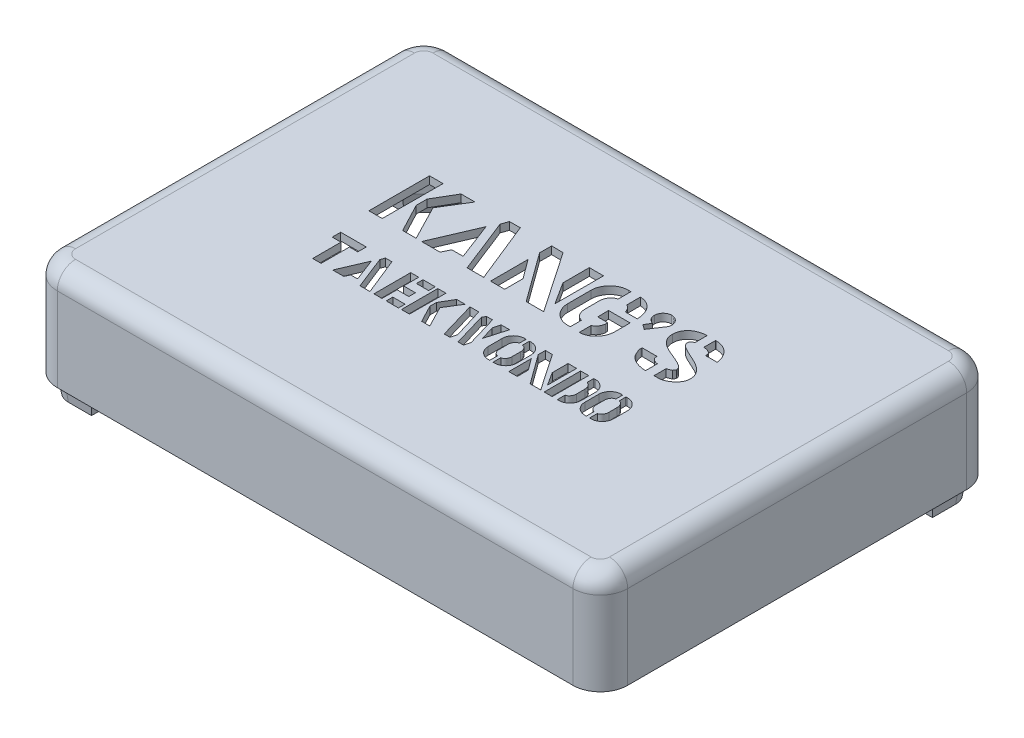
SolidWorks part; units mm, degrees
ref_plane "Front Plane" through (0, 0, 0) normal (0, 0, 1) x (1, 0, 0)
ref_plane "Top Plane" through (0, 0, 0) normal (0, 1, 0) x (1, 0, 0)
ref_plane "Right Plane" through (0, 0, 0) normal (1, 0, 0) x (0, 0, -1)
sketch "Sketch1" plane through (0, 0, 0) normal (0, 1, 0) x (1, 0, 0)
  line L0 (-44.0749, -23.5444) -> (-44.0749, 32.2128)
  line L1 (-39.5749, -26.5444) -> (45.2212, -26.5444)
  line L2 (-42.5749, -23.5444) -> (-42.5749, 32.2128)
  line L3 (-39.5749, 35.2128) -> (45.2212, 35.2128)
  line L4 (48.2212, -23.5444) -> (48.2212, 32.2128)
  line L5 (-42.5749, -26.5444) -> (48.2212, 35.2128) construction
  line L6 (-42.5749, 35.2128) -> (48.2212, -26.5444) construction
  line L7 (-39.5749, 36.7128) -> (45.2212, 36.7128)
  line L8 (49.7212, -23.5444) -> (49.7212, 32.2128)
  line L9 (-39.5749, -28.0444) -> (45.2212, -28.0444)
  arc A0 (45.2212, -26.5444) -> (48.2212, -23.5444) centre (45.2212, -23.5444) ccw
  arc A1 (-39.5749, -26.5444) -> (-42.5749, -23.5444) centre (-39.5749, -23.5444) cw
  arc A2 (-42.5749, 32.2128) -> (-39.5749, 35.2128) centre (-39.5749, 32.2128) cw
  arc A3 (45.2212, 35.2128) -> (48.2212, 32.2128) centre (45.2212, 32.2128) cw
  arc A4 (-44.0749, 32.2128) -> (-39.5749, 36.7128) centre (-39.5749, 32.2128) cw
  arc A5 (45.2212, 36.7128) -> (49.7212, 32.2128) centre (45.2212, 32.2128) cw
  arc A6 (45.2212, -28.0444) -> (49.7212, -23.5444) centre (45.2212, -23.5444) ccw
  arc A7 (-39.5749, -28.0444) -> (-44.0749, -23.5444) centre (-39.5749, -23.5444) cw
  arc A8 (45.2102, -26.5444) -> (48.2212, -23.5554) centre (45.2212, -23.5444) ccw construction
  arc A9 (-39.5639, 35.2128) -> (-42.5748, 32.2238) centre (-39.5749, 32.2128) ccw construction
  point P0 (0, 0)
  point P32 (117.5187, -35.5622)
  point P33 (48.386, -26.3869)
  dimension "D1" = 3
  dimension "D2" = 1.5
extrude "Boss-Extrude1" add sketch "Sketch1" along normal blind 1.25 contours A7 L9 A6 L8 A5 L7 A4 L0 L3 A3 L4 A0 L1 A1 L2 A2 | A3 L3 A2 L2 A1 L1 A0 L4 region at (-42.9351, 0, -4.3342) region at (2.8232, 0, -4.3342)
extrude "Boss-Extrude2" add sketch "Sketch1<3>" against normal up to surface (15.53 mm away)
sketch "Sketch1<3>" plane through (0, 0, 0) normal (0, 1, 0) x (1, 0, 0) same geometry as "Sketch1"
sketch "Sketch2" plane through (0, 0, -36.7128) normal (0, 0, -1) x (-1, 0, 0)
  line L5 (-34.9261, -2) -> (25.0435, -2)
  line L6 (-34.9261, -2) -> (-34.9261, -16.03)
  line L7 (-34.9261, -16.03) -> (25.0435, -16.03)
  line L30 (25.0435, -2) -> (25.0435, -16.03)
  line L36 (-21.1762, -3) -> (-34.4261, -3) construction
  line L37 (-34.4261, -15.53) -> (-34.4261, -3) construction
  line L40 (-21.1762, -15.53) -> (-34.4261, -15.53) construction
  line L41 (24.5435, -15.53) -> (24.5435, -3) construction
  dimension "D2" = 1
  dimension "D3" = 0.5
  dimension "D6" = 0.5
  dimension "D1" = 0.5
extrude "Cut-Extrude1" cut sketch "Sketch2" against normal up to next
sketch "Sketch3" plane through (0, 0, 0) normal (0, -1, 0) x (1, 0, 0)
  line L0 (-35.2393, -31.4128) -> (-38.7749, -27.8772)
  line L1 (-38.7749, 19.2089) -> (-35.2393, 22.7444)
  line L2 (40.8857, -31.4128) -> (44.4212, -27.8772)
  line L3 (45.2212, -35.4128) -> (40.8857, -35.4128)
  line L4 (40.8857, -35.4128) -> (40.8857, -31.4128)
  line L5 (48.4212, -32.2128) -> (48.4212, -27.8772)
  line L6 (48.4212, -27.8772) -> (44.4212, -27.8772)
  line L7 (-39.5749, -35.4128) -> (-35.2393, -35.4128)
  line L8 (-35.2393, -35.4128) -> (-35.2393, -31.4128)
  line L9 (-42.7749, -32.2128) -> (-42.7749, -27.8772)
  line L10 (-42.7749, -27.8772) -> (-38.7749, -27.8772)
  line L11 (-42.7749, 23.5444) -> (-42.7749, 19.2089)
  line L12 (-42.7749, 19.2089) -> (-38.7749, 19.2089)
  line L13 (-35.2393, 22.7444) -> (-35.2393, 26.7444)
  line L14 (-35.2393, 26.7444) -> (-39.5749, 26.7444)
  arc A0 (48.4212, -32.2128) -> (45.2212, -35.4128) centre (45.2212, -32.2128) cw
  arc A1 (45.2212, -35.2128) -> (48.2212, -32.2128) centre (45.2212, -32.2128) ccw construction
  arc A3 (-39.5749, -35.4128) -> (-42.7749, -32.2128) centre (-39.5749, -32.2128) cw
  arc A4 (-42.5749, -32.2128) -> (-39.5749, -35.2128) centre (-39.5749, -32.2128) ccw construction
  arc A5 (-42.7749, 23.5444) -> (-39.5749, 26.7444) centre (-39.5749, 23.5444) cw
  arc A6 (-39.5749, 26.5444) -> (-42.5749, 23.5444) centre (-39.5749, 23.5444) ccw construction
  dimension "D1" = 0.2
  dimension "D2" = 5
  dimension "D3" = 4
extrude "Boss-Extrude3" add sketch "Sketch3" along normal up to surface (15.53 mm away) up to face at (3.2468, -15.53, -10.6599)
extrude "Boss-Extrude4" add sketch "Sketch3<3>" along normal blind 3 draft 10 from surface starting at face at (0.2758, -15.53, -10.9565)
sketch "Sketch3<3>" plane through (0, 0, 0) normal (0, -1, 0) x (1, 0, 0) same geometry as "Sketch3"
fillet "Fillet1" radius 3 22 edges at (-42.7568, 1.25, -35.3948) (-44.0749, 1.25, -4.3342) (-42.7568, 1.25, 26.7264) (2.8232, 1.25, 28.0444) (48.4032, 1.25, 26.7264) (49.7212, 1.25, -4.3342) (48.4032, 1.25, -35.3948) (2.8232, 1.25, -36.7128) (-42.5749, 0, -4.3342) (2.8232, 0, -35.2128) (48.2212, 0, -2.1664) (47.3425, 0, 25.6657) (4.9909, 0, 26.5444) (-35.2393, 0, -33.3128) (-37.0071, 0, -29.645) (-40.6749, 0, -27.8772) (-40.6749, 0, 19.2089) (-37.0071, 0, 20.9766) (-35.2393, 0, 24.6444) (46.3212, 0, -27.8772) (42.6535, 0, -29.645) (40.8857, 0, -33.3128)
sketch "Sketch4" plane through (0, -15.53, 0) normal (0, -1, 0) x (1, 0, 0)
  line L0 (45.2212, -36.7128) -> (34.9261, -36.7128) construction
  line L1 (37.9225, -36.7128) -> (43.8922, -36.7128)
  line L2 (37.9225, -36.7128) -> (37.9225, -28.4366)
  line L3 (37.9225, -28.4366) -> (43.8618, -28.4366)
  line L4 (43.8922, -36.7128) -> (43.8618, -28.4366)
  line L5 (43.3856, -34.9085) -> (43.3458, -24.0628) construction
  line L6 (44.4212, -27.8772) -> (40.8857, -31.4128) construction
  point P8 (43.8618, -36.7128)
  dimension "D1" = 0.5
extrude "Cut-Extrude2" cut sketch "Sketch4" along normal through all
sketch "Sketch5" plane through (0, 1.25, 0) normal (0, 1, 0) x (1, 0, 0)
  line L0 (-41.0749, 5.9404) -> (46.7212, 5.9404) construction
  line L1 (-41.0749, -5.4272) -> (46.7212, -5.4272) construction
  line L2 (-41.0749, 32.2128) -> (-41.0749, -23.5444) construction
  line L3 (46.7212, -23.5444) -> (46.7212, 32.2128) construction
  text T0 "KANG'S" font "Stencil Gothic" height 10
  text T1 "TAEKWONDO" font "Stencil Gothic" height 6
extrude "Cut-Extrude3" cut sketch "Sketch5" against normal through all
